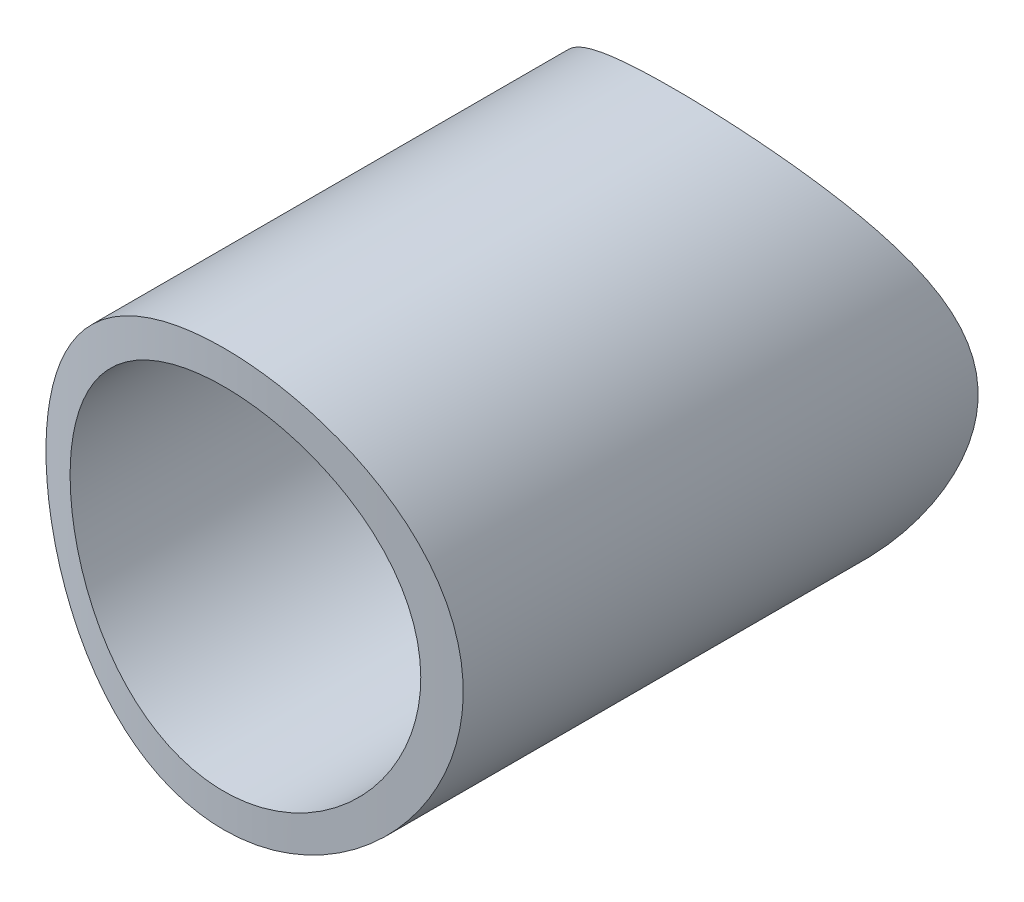
SolidWorks part; units mm, degrees
material "PTFE (general)"
ref_plane "Front Plane" through (0, 0, 0) normal (0, 0, 1) x (1, 0, 0)
ref_plane "Top Plane" through (0, 0, 0) normal (0, 1, 0) x (1, 0, 0)
ref_plane "Right Plane" through (0, 0, 0) normal (1, 0, 0) x (0, 0, -1)
sketch "Sketch1" plane through (0, 0, 0) normal (0, 0, 1) x (1, 0, 0)
  circle A0 centre (0, 0) radius 10.53
  circle A1 centre (0, 0) radius 12.53
  dimension "D1" = 21.06
  dimension "D2" = 2
extrude "Boss-Extrude1" add sketch "Sketch1" along normal blind 60
sketch "Sketch2" plane through (0, 0, 0) normal (0, 1, 0) x (1, 0, 0)
  circle A0 centre (0, 0) radius 16.5
  circle A1 centre (0, 0) radius 43.5
  circle A2 centre (0, 0) radius 74.5897
  dimension "D1" = 33
  dimension "D2" = 87
extrude "Cut-Extrude1" cut sketch "Sketch2" against normal through all both and the other way through all contours A2 A1 | A0 region at (0, 0, 0) region at (-72.48, 0, 0)
